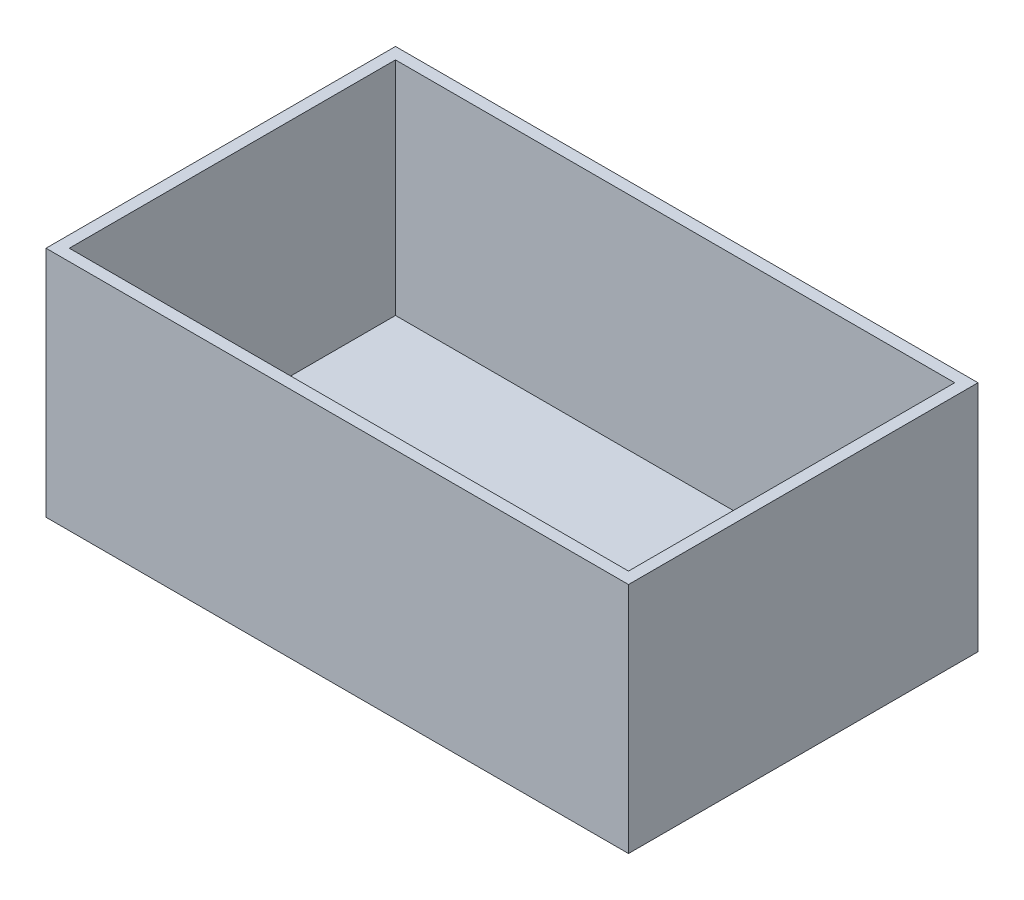
SolidWorks part; units mm, degrees
material "Balsa"
ref_plane "Front Plane" through (0, 0, 0) normal (0, 0, 1) x (1, 0, 0)
ref_plane "Top Plane" through (0, 0, 0) normal (0, 1, 0) x (1, 0, 0)
ref_plane "Right Plane" through (0, 0, 0) normal (1, 0, 0) x (0, 0, -1)
sketch "Sketch1" plane through (0, 0, 0) normal (0, 0, 1) x (1, 0, 0)
  line L1 (-250, -100) -> (250, -100)
  line L2 (-250, -100) -> (-250, 100)
  line L3 (-250, 100) -> (250, 100)
  line L4 (250, -100) -> (250, 100)
  line L5 (-250, -100) -> (250, 100) construction
  line L6 (-250, 100) -> (250, -100) construction
  point P0 (0, 0)
  dimension "D1" = 500
  dimension "D2" = 200
extrude "Boss-Extrude1" add sketch "Sketch1" along normal blind 300
sketch "Sketch2" plane through (0, 0, 0) normal (0, 1, 0) x (1, 0, 0)
  line L0 (25, 0) -> (25, 30)
  line L1 (0, 299.8873) -> (0, -668.1731) construction
  line L2 (25, 30) -> (-25, 30)
  line L3 (35, 0) -> (35, 40)
  line L4 (35, 40) -> (-35, 40)
  line L5 (35, 0) -> (25, 0)
  line L6 (-25, 0) -> (-25, 30)
  line L7 (-35, 0) -> (-25, 0)
  line L8 (-35, 0) -> (-35, 40)
  point P9 (0, 30)
  point P13 (0, 40)
  dimension "D1" = 10
  dimension "D2" = 10
  dimension "D3" = 25
  dimension "D4" = 30
extrude "Boss-Extrude2" add sketch "Sketch2" along normal blind 20 and the other way blind 20
shell "Shell1" thickness 10 removed face at (0, 100, 150)
